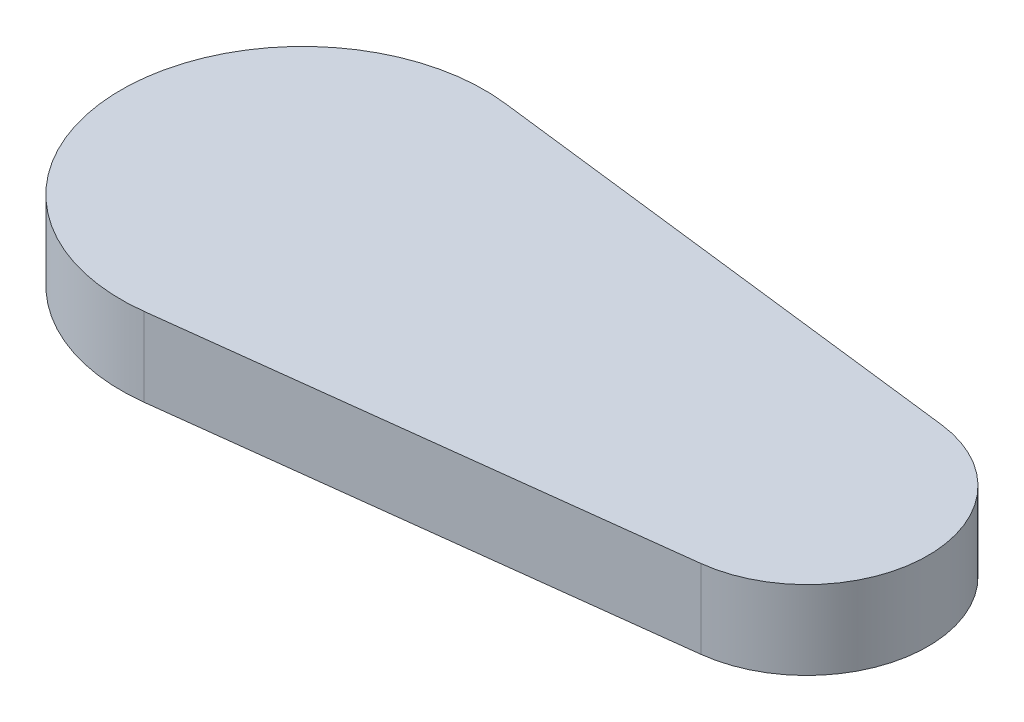
SolidWorks part; units mm, degrees
ref_plane "Płaszczyzna przednia" through (0, 0, 0) normal (0, 0, 1) x (1, 0, 0)
ref_plane "Płaszczyzna górna" through (0, 0, 0) normal (0, 1, 0) x (1, 0, 0)
ref_plane "Płaszczyzna prawa" through (0, 0, 0) normal (1, 0, 0) x (0, 0, -1)
sketch "Sketch1" plane through (0, 0, 0) normal (0, 1, 0) x (1, 0, 0)
  line L0 (0.7207, 5.9566) -> (17.1305, 3.971)
  line L1 (0.7207, -5.9566) -> (17.1305, -3.971)
  circle A0 centre (0, 0) radius 6
  circle A1 centre (16.65, 0) radius 4
  dimension "D1" = 8
  dimension "D2" = 12
  dimension "D3" = 16.65
extrude "Boss-Extrude1" add sketch "Sketch1" along normal blind 2.6 contours A0 | A1 | A1 L0 A0 L1 region at (9.1082, 0, 0) region at (0, 0, 0) region at (16.65, 0, 0)
